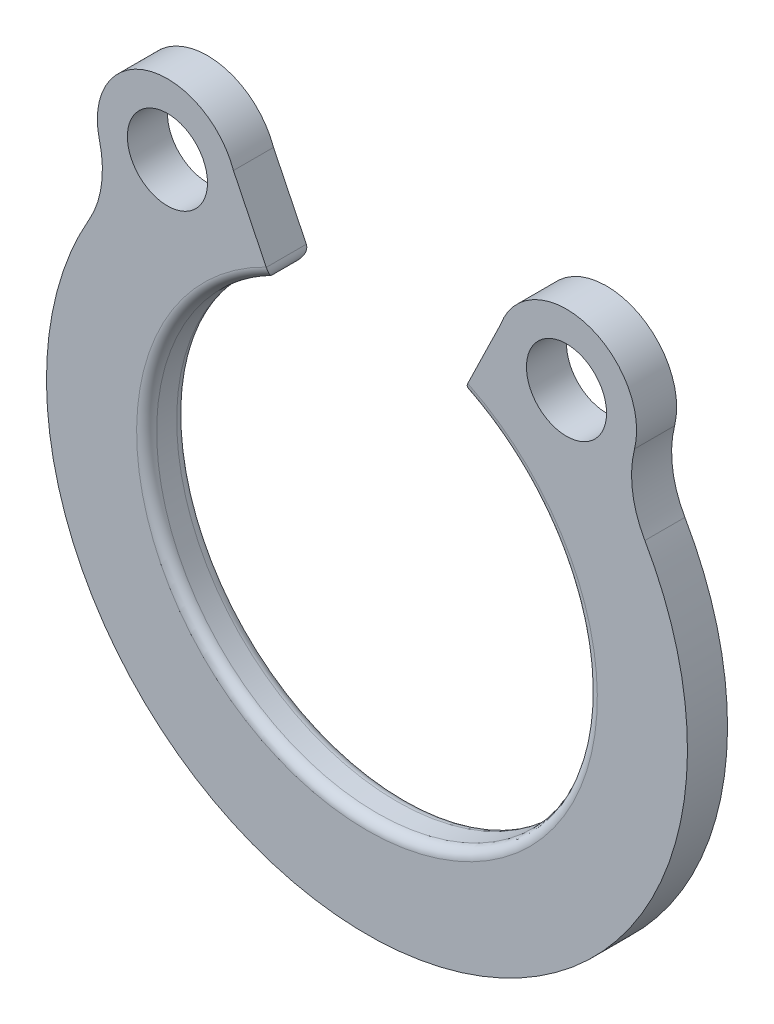
SolidWorks part; units mm, degrees
ref_plane "Front Plane" through (0, 0, 0) normal (0, 0, 1) x (1, 0, 0)
ref_plane "Top Plane" through (0, 0, 0) normal (0, 1, 0) x (1, 0, 0)
ref_plane "Right Plane" through (0, 0, 0) normal (1, 0, 0) x (0, 0, -1)
sketch "Sketch1" plane through (0, 0, 0) normal (0, 0, 1) x (1, 0, 0)
  line L2 (3.5, 7.1937) -> (0, 0)
  line L3 (0, 0) -> (-3.5, 7.1937)
  line L4 (-1.75, 3.5969) -> (1.75, 3.5969) construction
  circle A0 centre (0, 0) radius 8
  circle A1 centre (0, 0) radius 5.5
  dimension "D1" = 16
  dimension "D2" = 2.5
  dimension "D3" = 7
extrude "Boss-Extrude1" add sketch "Sketch1" along normal blind 0.5 and the other way blind 0.5 contours A1 L3 A0 L2 region at (6.5953, 4.1256, 0)
sketch "Sketch2" plane through (0, 0, 0) normal (0, 0, 1) x (1, 0, 0)
  arc A2 (-3.5, 7.1937) -> (3.5, 7.1937) centre (0, 0) ccw construction
  circle A3 centre (-4.9805, 6.2606) radius 1.75
  circle A5 centre (-4.9805, 6.2606) radius 1
  circle A6 centre (4.9805, 6.2606) radius 1.75
  circle A7 centre (4.9805, 6.2606) radius 1
  point P2 (5.4369, 5.8686)
  point P9 (-5.197, 6.082)
  dimension "D1" = 2
  dimension "D2" = 0.75
extrude "Boss-Extrude2" add sketch "Sketch2" along normal up to surface (0.5 mm away) and the other way up to surface (0.5 mm away) up to face at (0, -0.3401, 0.5) other way up to face at (0, -0.3401, -0.5)
fillet "Fillet1" radius 2.5 2 edges at (-6.2226, 5.0279, 0) (6.2226, 5.0279, 0)
extrude "Cut-Extrude1" cut sketch "Sketch2<2>" against normal through all both and the other way through all contours A5 | A7 region at (-4.9805, 6.2606, 0) region at (4.9805, 6.2606, 0)
sketch "Sketch2<2>" plane through (0, 0, 0) normal (0, 0, 1) x (1, 0, 0) same geometry as "Sketch2"
fillet "Fillet4" radius 0.25 4 edges at (0, -5.5, -0.5) (2.4063, 4.9457, 0) (0, -5.5, 0.5) (-2.4062, 4.9457, 0)
